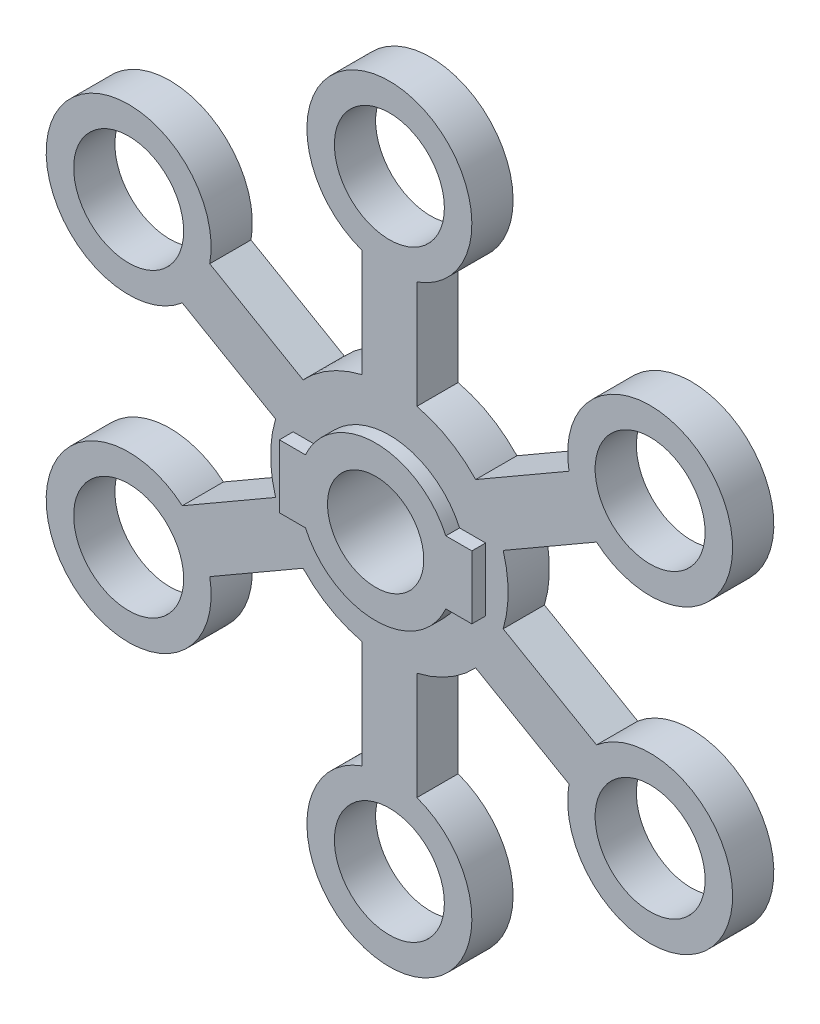
SolidWorks part; units mm, degrees
ref_plane "Front Plane" through (0, 0, 0) normal (0, 0, 1) x (1, 0, 0)
ref_plane "Top Plane" through (0, 0, 0) normal (0, 1, 0) x (1, 0, 0)
ref_plane "Right Plane" through (0, 0, 0) normal (1, 0, 0) x (0, 0, -1)
sketch "Sketch2" plane through (0, 0, 0) normal (0, 0, 1) x (1, 0, 0)
  line L0 (0, 0) -> (0, 47430.167) construction
  line L1 (0, 0) -> (47430.167, 0) construction
  line L2 (-10, 81.2157) -> (-10, 42.023)
  line L3 (10, 81.2157) -> (10, 42.023)
  line L4 (65.3349, 49.2681) -> (31.393, 29.6717)
  line L5 (75.3349, 31.9476) -> (41.393, 12.3512)
  line L6 (75.3349, -31.9476) -> (41.393, -12.3512)
  line L7 (65.3349, -49.2681) -> (31.393, -29.6717)
  line L8 (10, -81.2157) -> (10, -42.023)
  line L9 (-10, -81.2157) -> (-10, -42.023)
  line L10 (-65.3349, -49.2681) -> (-31.393, -29.6717)
  line L11 (-75.3349, -31.9476) -> (-41.393, -12.3512)
  line L12 (-75.3349, 31.9476) -> (-41.393, 12.3512)
  line L13 (-65.3349, 49.2681) -> (-31.393, 29.6717)
  line L14 (25.5294, -11.5) -> (35, -11.5)
  line L15 (-35, 11.5) -> (-25.5294, 11.5)
  line L16 (-35, 11.5) -> (-35, -11.5)
  line L17 (-35, -11.5) -> (-25.5294, -11.5)
  line L18 (35, 11.5) -> (35, -11.5)
  line L19 (-35, 11.5) -> (35, -11.5) construction
  line L20 (-35, -11.5) -> (35, 11.5) construction
  line L21 (25.5294, 11.5) -> (35, 11.5)
  arc A0 (-25.5294, -11.5) -> (25.5294, -11.5) centre (0, 0) ccw
  arc A1 (-10, 42.023) -> (-31.393, 29.6717) centre (0, 0) ccw
  circle A2 centre (0, 0) radius 109.5 construction
  circle A3 centre (0, 109.5) radius 20
  arc A4 (10, 81.2157) -> (-10, 81.2157) centre (0, 109.5) ccw
  circle A5 centre (94.8298, 54.75) radius 20
  arc A6 (75.3349, 31.9476) -> (65.3349, 49.2681) centre (94.8298, 54.75) ccw
  circle A7 centre (94.8298, -54.75) radius 20
  arc A8 (65.3349, -49.2681) -> (75.3349, -31.9476) centre (94.8298, -54.75) ccw
  circle A9 centre (0, -109.5) radius 20
  arc A10 (-10, -81.2157) -> (10, -81.2157) centre (0, -109.5) ccw
  circle A11 centre (-94.8298, -54.75) radius 20
  arc A12 (-75.3349, -31.9476) -> (-65.3349, -49.2681) centre (-94.8298, -54.75) ccw
  circle A13 centre (-94.8298, 54.75) radius 20
  arc A14 (-65.3349, 49.2681) -> (-75.3349, 31.9476) centre (-94.8298, 54.75) ccw
  arc A15 (31.393, 29.6717) -> (10, 42.023) centre (0, 0) ccw
  arc A16 (-41.393, 12.3512) -> (-41.393, -12.3512) centre (0, 0) ccw
  arc A17 (-31.393, -29.6717) -> (-10, -42.023) centre (0, 0) ccw
  arc A18 (10, -42.023) -> (31.393, -29.6717) centre (0, 0) ccw
  arc A19 (41.393, -12.3512) -> (41.393, 12.3512) centre (0, 0) ccw
  arc A20 (25.5294, 11.5) -> (-25.5294, 11.5) centre (0, 0) ccw
  circle A21 centre (0, 0) radius 17.5
  point P16 (10, 61.6193)
  point P47 (0, 0)
  dimension "D1" = 56
  dimension "D2" = 86.3928
  dimension "D3" = 219
  dimension "D4" = 60
  dimension "D5" = 40
  dimension "D10" = 35
  dimension "D6" = 20
  dimension "D7" = 6
  dimension "D8" = 35
  dimension "D9" = 23
extrude "Boss-Extrude2" add sketch "Sketch2" along normal mid plane 25 contours L21 A20 L15 L16 L17 A0 L14 L18 A21 region at (0, -27.1036, 0)
extrude "Boss-Extrude5" add sketch "Sketch2<5>" along normal mid plane 15 contours L6 A19 L5 A6 L4 A15 L3 A4 L2 A1 L13 A14 L12 A16 L11 A12 L10 A17 L9 A10 L8 A18 L7 A8 A20 L21 L18 L14 A0 L17 L16 L15 A3 A5 A7 A9 A11 A13 region at (0, 135.7561, 0)
sketch "Sketch2<5>" plane through (0, 0, 0) normal (0, 0, 1) x (1, 0, 0) same geometry as "Sketch2"
